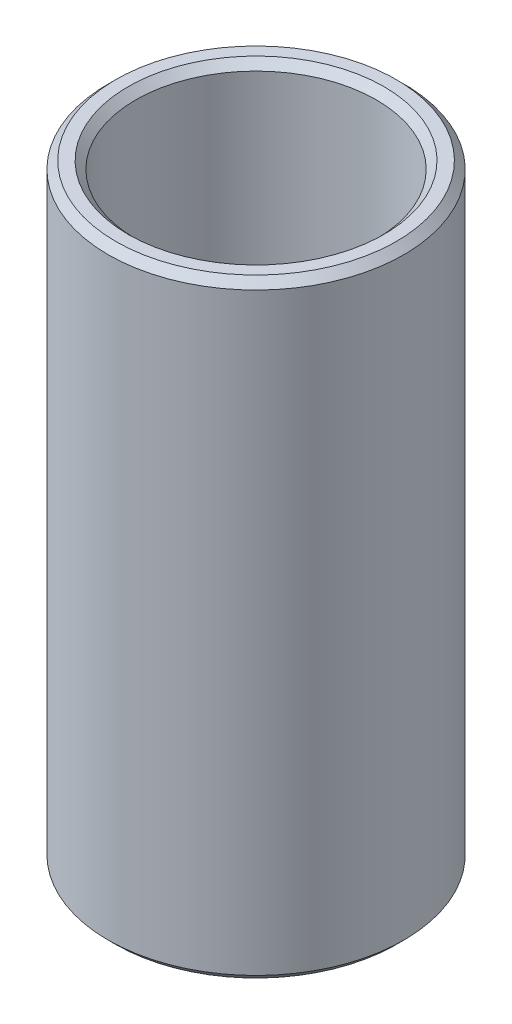
SolidWorks part; units mm, degrees
ref_plane "Front Plane" through (0, 0, 0) normal (0, 0, 1) x (1, 0, 0)
ref_plane "Top Plane" through (0, 0, 0) normal (0, 1, 0) x (1, 0, 0)
ref_plane "Right Plane" through (0, 0, 0) normal (1, 0, 0) x (0, 0, -1)
sketch "Sketch1" plane through (0, 0, 0) normal (0, 1, 0) x (1, 0, 0)
  circle A0 centre (0, 0) radius 40
  dimension "SLEEVE_OD" = 80
extrude "Boss-Extrude1" add sketch "Sketch1" along normal blind 164.6697
sketch "Sketch2" plane through (0, 0, 0) normal (0, 1, 0) x (1, 0, 0)
  circle A0 centre (0, 0) radius 32.5498
  dimension "BORE_D" = 65.0995
extrude "Cut-Extrude1" cut sketch "Sketch2" along normal through all
chamfer "Chamfer1" distance 2.0624 angle 45 4 edges at (0, 164.6697, 32.5498) (0, 0, 32.5498) (0, 0, 40) (0, 164.6697, 40)
